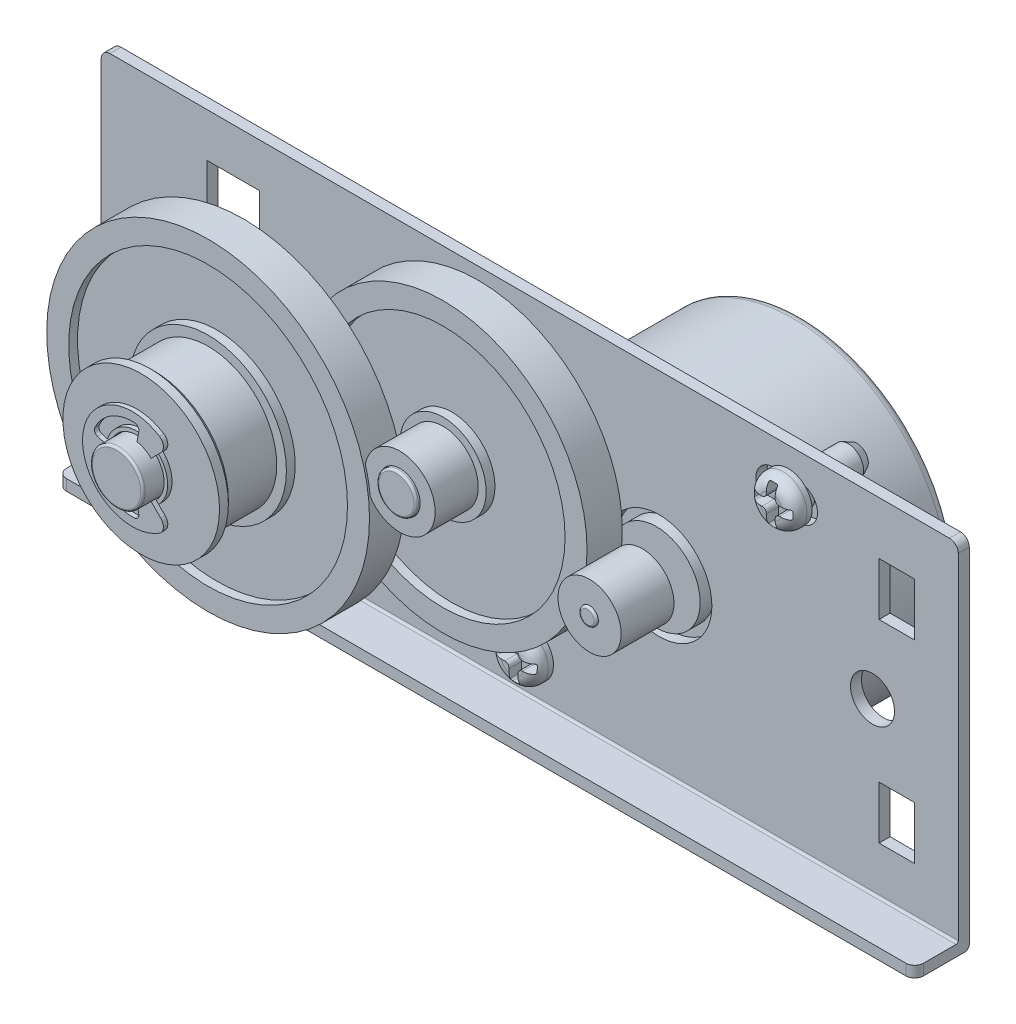
SolidWorks part; units mm, degrees
ref_plane "Plano frontal" through (0, 0, 0) normal (0, 0, 1) x (1, 0, 0)
ref_plane "Plano superior" through (0, 0, 0) normal (0, 1, 0) x (1, 0, 0)
ref_plane "Plano direito" through (0, 0, 0) normal (1, 0, 0) x (0, 0, -1)
sketch "Esboço1" plane through (0, 0, 0) normal (0, 0, 1) x (1, 0, 0)
  line L1 (48.7, 0.625) -> (-48.7, 0.625)
  line L2 (48.7, 0.625) -> (48.7, -0.625)
  line L3 (48.7, -0.625) -> (-48.7, -0.625)
  line L4 (-48.7, 0.625) -> (-48.7, -0.625)
  line L5 (48.7, 0.625) -> (-48.7, -0.625) construction
  line L6 (48.7, -0.625) -> (-48.7, 0.625) construction
  point P0 (0, 0)
  dimension "D1" = 97.4
  dimension "D2" = 1.25
extrude "Ressalto-extrusão1" add sketch "Esboço1" along normal blind 6.2
sketch "Esboço2" plane through (0, -0.625, 0) normal (0, 1, 0) x (1, 0, 0)
  line L0 (48.7, -6.2) -> (48.7, 0) construction
  line L1 (-48.7, 0) -> (48.7, 0)
  line L2 (-48.7, 0) -> (-48.7, -1.25)
  line L3 (-48.7, -1.25) -> (48.7, -1.25)
  line L4 (48.7, 0) -> (48.7, -1.25)
  dimension "D1" = 1.25
extrude "Ressalto-extrusão2" add sketch "Esboço2" along normal blind 40.6 contours L3 L4 L1 L2
fillet "Filete1" radius 1 4 edges at (48.7, 39.975, 0.625) (-48.7, 39.975, 0.625) (48.7, 0, 6.2) (-48.7, 0, 6.2)
sketch "Esboço3" plane through (0, 0, 1.25) normal (0, 0, 1) x (1, 0, 0)
  line L0 (27.7, 34.975) -> (30.7, 34.975) construction
  line L11 (39.7, 33.975) -> (43.7, 33.975)
  line L12 (39.7, 33.975) -> (39.7, 27.975)
  line L13 (39.7, 27.975) -> (43.7, 27.975)
  line L14 (43.7, 33.975) -> (43.7, 27.975)
  line L15 (39.7, 11.975) -> (43.7, 11.975)
  line L16 (39.7, 11.975) -> (39.7, 5.975)
  line L17 (39.7, 5.975) -> (43.7, 5.975)
  line L18 (43.7, 11.975) -> (43.7, 5.975)
  line L19 (-36.7, 12.975) -> (-30.7, 12.975)
  line L20 (-36.7, 12.975) -> (-36.7, 4.975)
  line L21 (-36.7, 4.975) -> (-30.7, 4.975)
  line L22 (-30.7, 12.975) -> (-30.7, 4.975)
  line L23 (27.7, 36.975) -> (30.7, 36.975)
  line L24 (27.7, 32.975) -> (30.7, 32.975)
  line L25 (0, 39.975) -> (0, 2.975) construction
  line L26 (-47.7, 39.975) -> (47.7, 39.975) construction
  line L27 (-47.7, 39.975) -> (47.7, 39.975) construction
  line L28 (-48.7, 38.975) -> (-48.7, 0.625) construction
  line L29 (-36.7, 34.975) -> (-30.7, 34.975)
  line L30 (-36.7, 34.975) -> (-36.7, 26.975)
  line L31 (-36.7, 26.975) -> (-30.7, 26.975)
  line L32 (-30.7, 34.975) -> (-30.7, 26.975)
  line L33 (48.7, 38.975) -> (48.7, 0.625) construction
  line L34 (48.7, 19.8) -> (0, 19.8) construction
  circle A5 centre (-43.7, 4.975) radius 2
  circle A6 centre (0, 4.975) radius 2
  circle A7 centre (38.95, 19.8) radius 2.5
  circle A8 centre (14.7, 19.8) radius 6
  arc A9 (27.7, 36.975) -> (27.7, 32.975) centre (27.7, 34.975) ccw
  arc A10 (30.7, 32.975) -> (30.7, 36.975) centre (30.7, 34.975) ccw
  point P22 (29.2, 34.975)
  point P33 (25.7, 34.975)
  point P34 (32.7, 34.975)
  dimension "D14" = 5
  dimension "D16" = 16
  dimension "D27" = 4
  dimension "D3" = 4
  dimension "D6" = 12
  dimension "D17" = 5
  dimension "D4" = 35
  dimension "D8" = 34
  dimension "D9" = 6
  dimension "D10" = 4
  dimension "D11" = 6
  dimension "D12" = 4
  dimension "D13" = 5
  dimension "D15" = 6
  dimension "D18" = 9.75
  dimension "D19" = 8
  dimension "D20" = 6
  dimension "D21" = 8
  dimension "D22" = 6
  dimension "D23" = 12
  dimension "D24" = 12
  dimension "D25" = 5
  dimension "D26" = 14
  dimension "D28" = 5
  dimension "D29" = 35
  dimension "D30" = 0
  dimension "D31" = 4
  dimension "D32" = 7
  dimension "D33" = 3
  dimension "D34" = 16
extrude "Corte-extrusão1" cut sketch "Esboço3" against normal blind 40.6
sketch "Esboço5" plane through (0, 0, 0) normal (0, 0, -1) x (-1, 0, 0)
  line L0 (-20.7, 19.8) -> (48.7, 19.8) construction
  line L1 (48.7, 38.975) -> (48.7, -0.625) construction
  line L2 (47.7, 39.975) -> (-47.7, 39.975) construction
  line L3 (48.7, 23.975) -> (48.7, 19.8) construction
  circle A0 centre (4.1, 23.975) radius 2
  circle A1 centre (25.7, 19.8) radius 3
  circle A2 centre (-14.7, 19.8) radius 6 construction
  dimension "D1" = 23
  dimension "6" = 6
  dimension "D2" = 4
  dimension "D3" = 16
  dimension "D4" = 44.6
sketch "Esboço6" plane through (0, 0, 0) normal (0, 0, -1) x (-1, 0, 0)
  circle A0 centre (25.7, 19.8) radius 3
  dimension "D1" = 6
extrude "Ressalto-extrusão3" add sketch "Esboço6" against normal blind 22.5
sketch "Esboço7" plane through (0, 0, 0) normal (0, 0, -1) x (-1, 0, 0)
  circle A0 centre (4.1, 23.975) radius 2.25
  dimension "D1" = 4.5
extrude "Ressalto-extrusão4" add sketch "Esboço7" against normal blind 12.3
fillet "Filete2" radius 0.25 2 edges at (-6.35, 23.975, 12.3) (-28.7, 19.8, 22.5)
sketch "Esboço12" plane through (0, 0, 0) normal (0, 0, 1) x (1, 0, 0)
  circle A0 centre (-4.1, 23.975) radius 4
  dimension "D1" = 8
extrude "Ressalto-extrusão7" add sketch "Esboço12" along normal blind 3
sketch "Esboço13" plane through (0, 0, 0) normal (0, 0, -1) x (-1, 0, 0)
  circle A0 centre (25.7, 19.8) radius 4.5
  dimension "D1" = 9
extrude "Ressalto-extrusão8" add sketch "Esboço13" against normal blind 8.1
sketch "Esboço8" plane through (0, 0, 3) normal (0, 0, 1) x (1, 0, 0)
  circle A0 centre (-4.1, 23.975) radius 16.365
  circle A1 centre (-4.1, 23.975) radius 2.3
  dimension "D1" = 32.73
  dimension "D2" = 4.6
extrude "Ressalto-extrusão5" add sketch "Esboço8" along normal blind 4
sketch "Esboço9" plane through (0, 0, 3) normal (0, 0, 1) x (1, 0, 0)
  circle A1 centre (-4.1, 23.975) radius 4
  circle A2 centre (-4.1, 23.975) radius 2.3
  dimension "D1" = 8
extrude "Ressalto-extrusão6" add sketch "Esboço9" along normal blind 8.9
sketch "Esboço10" plane through (0, 0, 7) normal (0, 0, 1) x (1, 0, 0)
  circle A0 centre (-4.1, 23.975) radius 4.9
  circle A1 centre (-4.1, 23.975) radius 13.865
  circle A2 centre (-4.1, 23.975) radius 16.365 construction
  dimension "D1" = 9.8
  dimension "D2" = 2.5
extrude "Corte-extrusão2" cut sketch "Esboço10" against normal blind 1
sketch "Esboço11" plane through (0, 0, 3) normal (0, 0, -1) x (-1, 0, 0)
  circle A1 centre (4.1, 23.975) radius 13.86
  circle A2 centre (4.1, 23.975) radius 4.9
extrude "Corte-extrusão3" cut sketch "Esboço11" against normal blind 1
sketch "Esboço14" plane through (0, 0, 8.1) normal (0, 0, 1) x (1, 0, 0)
  circle A0 centre (-25.7, 19.8) radius 18.34
  circle A1 centre (-25.7, 19.8) radius 3.1
  circle A2 centre (-25.7, 19.8) radius 3 construction
  dimension "D1" = 36.68
  dimension "D2" = 0.1
extrude "Ressalto-extrusão9" add sketch "Esboço14" along normal blind 4
sketch "Esboço15" plane through (0, 0, 8.1) normal (0, 0, 1) x (1, 0, 0)
  circle A0 centre (-25.7, 19.8) radius 7.8
  circle A1 centre (-25.7, 19.8) radius 3.1
  dimension "D1" = 15.6
extrude "Ressalto-extrusão10" add sketch "Esboço15" along normal blind 11.6
sketch "Esboço16" plane through (0, 0, 19.7) normal (0, 0, 1) x (1, 0, 0)
  circle A0 centre (-25.7, 19.8) radius 3.1
  circle A1 centre (-25.7, 19.8) radius 8.9
  dimension "D1" = 17.8
extrude "Ressalto-extrusão11" add sketch "Esboço16" against normal blind 1.5
chamfer "Chanfro1" distance 0.5 angle 45 1 edges at (-16.8, 19.8, 18.2)
sketch "Esboço17" plane through (0, 0, 19.7) normal (0, 0, 1) x (1, 0, 0)
  circle A0 centre (-25.7, 19.8) radius 3.1
  circle A1 centre (-25.7, 19.8) radius 3.5
  dimension "D1" = 7
extrude "Ressalto-extrusão12" add sketch "Esboço17" along normal blind 0.5
sketch "Esboço18" plane through (0, 0, 12.1) normal (0, 0, 1) x (1, 0, 0)
  circle A0 centre (-25.7, 19.8) radius 15.84
  circle A1 centre (-25.7, 19.8) radius 8.9
  circle A2 centre (-25.7, 19.8) radius 18.34 construction
  dimension "D1" = 2.5
  dimension "D2" = 17.8
extrude "Corte-extrusão4" cut sketch "Esboço18" against normal blind 1
sketch "Esboço19" plane through (0, 0, 8.1) normal (0, 0, -1) x (-1, 0, 0)
  circle A0 centre (25.7, 19.8) radius 8.9
  circle A1 centre (25.7, 19.8) radius 15.825
extrude "Corte-extrusão5" cut sketch "Esboço19" against normal blind 1
sketch "Esboço20" plane through (0, 0, 20.2) normal (0, 0, 1) x (1, 0, 0)
  line L0 (-28.3227, 20.6269) -> (-29.675, 21.0533)
  line L3 (-23.7555, 21.7445) -> (-22.4747, 23.0253)
  line L4 (-25.2225, 22.5082) -> (-24.9763, 23.9046)
  line L5 (-23.7555, 17.8555) -> (-22.4747, 16.5747)
  line L6 (-25.2225, 17.0918) -> (-24.9763, 15.6954)
  line L7 (-28.3227, 18.9731) -> (-29.675, 18.5467)
  arc A0 (-22.6425, 24.5746) -> (-22.6425, 15.0254) centre (-25.7, 19.8) ccw
  arc A1 (-25.4411, 24.4906) -> (-29.9802, 21.7362) centre (-25.7, 19.8) ccw
  arc A2 (-28.3227, 20.6269) -> (-28.3227, 18.9731) centre (-25.7, 19.8) ccw
  arc A3 (-23.7555, 21.7445) -> (-25.2225, 22.5082) centre (-25.7, 19.8) ccw
  arc A4 (-25.2225, 17.0918) -> (-23.7555, 17.8555) centre (-25.7, 19.8) ccw
  arc A5 (-29.9802, 17.8638) -> (-25.4411, 15.1094) centre (-25.7, 19.8) ccw
  arc A6 (-22.4747, 16.5747) -> (-22.6425, 15.0254) centre (-23.1818, 15.8675) cw
  arc A7 (-22.4747, 23.0253) -> (-22.6425, 24.5746) centre (-23.1818, 23.7325) ccw
  arc A8 (-25.4411, 15.1094) -> (-24.9763, 15.6954) centre (-25.4687, 15.6086) ccw
  arc A9 (-25.4411, 24.4906) -> (-24.9763, 23.9046) centre (-25.4687, 23.9914) cw
  arc A10 (-29.9802, 17.8638) -> (-29.675, 18.5467) centre (-29.5246, 18.0698) cw
  arc A11 (-29.9802, 21.7362) -> (-29.675, 21.0533) centre (-29.5246, 21.5302) ccw
  dimension "D2" = 1
  dimension "D3" = 0.5
  dimension "D1" = 35
  dimension "D4" = 35
  dimension "D5" = 35
extrude "Ressalto-extrusão13" add sketch "Esboço20" along normal blind 0.5
sketch "Esboço21" plane through (0, 0, 0) normal (0, 0, -1) x (-1, 0, 0)
  line L0 (-29.3939, 34.975) -> (0, 4.975) construction
  line L1 (3.3061, 4.975) -> (-3.6939, 4.975) construction
  line L2 (3.5952, 5.1615) -> (2.7796, 20.8817)
  line L3 (-13.4337, 37.4293) -> (-29.134, 38.5656)
  line L4 (0, 1.375) -> (-4.8727, 1.375)
  line L5 (-32.9939, 34.975) -> (-32.9939, 30.076)
  line L6 (-32.9939, 30.076) -> (-30.4878, 27.5182)
  line L7 (-7.4776, 4.0335) -> (-4.8727, 1.375)
  circle A2 centre (0, 4.975) radius 1.75
  circle A3 centre (-29.3939, 34.975) radius 1.75
  arc A4 (-30.4878, 27.5182) -> (-7.4776, 4.0335) centre (-14.6969, 19.975) ccw
  arc A5 (0, 1.375) -> (3.5952, 5.1615) centre (0, 4.975) ccw
  arc A7 (-29.134, 38.5656) -> (-32.9939, 34.975) centre (-29.3939, 34.975) ccw
  arc A9 (2.7796, 20.8817) -> (-13.4337, 37.4293) centre (-14.6969, 19.975) ccw
  dimension "D2" = 3.5
  dimension "D3" = 3.5
  dimension "D4" = 35
  dimension "D5" = 7.2
  dimension "D1" = 42
  dimension "D7" = 6
extrude "Ressalto-extrusão14" add sketch "Esboço21" along normal blind 0.92
sketch "Esboço23" plane through (0, 0, 0) normal (0, 0, 1) x (1, 0, 0)
  circle A0 centre (14.7, 19.8) radius 17.675
extrude "Ressalto-extrusão15" add sketch "Esboço23" against normal blind 15
fillet "Filete4" radius 1 1 edges at (32.375, 19.8, -15)
sketch "Esboço24" plane through (0, 0, -0.92) normal (0, 0, -1) x (-1, 0, 0)
  circle A0 centre (0, 4.975) radius 1.75
  circle A1 centre (0, 4.975) radius 2.05
  circle A2 centre (-29.3939, 34.975) radius 1.75
  circle A3 centre (-29.3939, 34.975) radius 2.05
  dimension "D1" = 0.3
  dimension "D2" = 0.3
extrude "Ressalto-extrusão16" add sketch "Esboço24" along normal blind 1
sketch "Esboço25" plane through (0, 0, -15) normal (0, 0, -1) x (-1, 0, 0)
  circle A0 centre (-14.7, 19.8) radius 2.5
  dimension "D1" = 5
extrude "Ressalto-extrusão17" add sketch "Esboço25" along normal blind 0.1
sketch "Esboço26" plane through (0, 0, -15.1) normal (0, 0, -1) x (-1, 0, 0)
  circle A0 centre (-14.7, 19.8) radius 1
  dimension "D1" = 2
extrude "Ressalto-extrusão18" add sketch "Esboço26" along normal blind 0.5
fillet "Filete6" radius 0.1 1 edges at (12.2, 19.8, -15.1)
sketch "Esboço27" plane through (0, 0, -15) normal (0, 0, 1) x (1, 0, 0)
  circle A0 centre (14.7, 19.8) radius 4.99
  dimension "D1" = 9.98
extrude "Ressalto-extrusão19" add sketch "Esboço27" along normal blind 16.57
sketch "Esboço28" plane through (0, 0, -15.6) normal (0, 0, -1) x (-1, 0, 0)
  circle A0 centre (-14.7, 19.8) radius 1
extrude "Ressalto-extrusão20" add sketch "Esboço28" against normal blind 25
fillet "Filete5" radius 0.25 2 edges at (13.7, 19.8, -15.6) (13.7, 19.8, 9.4)
ref_plane "Plano2" through (0, 0, 9.15) normal (0, 0, 1) x (1, 0, 0)
sketch "Esboço29" plane through (0, 0, 9.15) normal (0, 0, 1) x (1, 0, 0)
  circle A0 centre (14.7, 19.8) radius 3.59
  dimension "D1" = 7.18
extrude "Ressalto-extrusão21" add sketch "Esboço29" against normal blind 6
sketch "Esboço30" plane through (0, 0, 1.25) normal (0, 0, 1) x (1, 0, 0)
  circle A0 centre (0, 4.975) radius 2.7
  circle A1 centre (29.3939, 34.975) radius 2.7
  dimension "D1" = 5.4
  dimension "D2" = 5.4
extrude "Ressalto-extrusão22" add sketch "Esboço30" along normal blind 2
fillet "Filete7" radius 1.4 2 edges at (2.7, 4.975, 3.25) (32.0939, 34.975, 3.25)
sketch "Esboço31" plane through (0, 0, 3.25) normal (0, 0, 1) x (1, 0, 0)
  line L1 (29.0939, 37.175) -> (29.6939, 37.175)
  line L2 (28.8939, 36.975) -> (28.8939, 35.975)
  line L3 (29.0939, 32.775) -> (29.6939, 32.775)
  line L4 (29.8939, 36.975) -> (29.8939, 35.975)
  line L7 (31.3939, 35.475) -> (30.3939, 35.475)
  line L8 (31.5939, 35.275) -> (31.5939, 34.675)
  line L9 (31.3939, 34.475) -> (30.3939, 34.475)
  line L10 (27.1939, 35.275) -> (27.1939, 34.675)
  line L15 (28.8939, 33.975) -> (28.8939, 32.975)
  line L17 (29.8939, 33.975) -> (29.8939, 32.975)
  line L18 (28.3939, 35.475) -> (27.3939, 35.475)
  line L19 (28.3939, 34.475) -> (27.3939, 34.475)
  line L42 (-0.1421, 7.325) -> (0.4579, 7.325)
  line L43 (-0.3421, 7.125) -> (-0.3421, 6.125)
  line L44 (-0.1421, 2.925) -> (0.4579, 2.925)
  line L45 (0.6579, 7.125) -> (0.6579, 6.125)
  line L46 (2.1579, 5.625) -> (1.1579, 5.625)
  line L47 (2.3579, 5.425) -> (2.3579, 4.825)
  line L48 (2.1579, 4.625) -> (1.1579, 4.625)
  line L49 (-2.0421, 5.425) -> (-2.0421, 4.825)
  line L50 (-0.3421, 4.125) -> (-0.3421, 3.125)
  line L51 (0.6579, 4.125) -> (0.6579, 3.125)
  line L52 (-0.8421, 5.625) -> (-1.8421, 5.625)
  line L53 (-0.8421, 4.625) -> (-1.8421, 4.625)
  arc A0 (29.8939, 33.975) -> (30.3939, 34.475) centre (30.3939, 33.975) cw
  arc A1 (28.8939, 33.975) -> (28.3939, 34.475) centre (28.3939, 33.975) ccw
  arc A2 (29.8939, 35.975) -> (30.3939, 35.475) centre (30.3939, 35.975) ccw
  arc A3 (28.8939, 35.975) -> (28.3939, 35.475) centre (28.3939, 35.975) cw
  arc A4 (28.8939, 32.975) -> (29.0939, 32.775) centre (29.0939, 32.975) ccw
  arc A5 (29.6939, 32.775) -> (29.8939, 32.975) centre (29.6939, 32.975) ccw
  arc A6 (31.5939, 34.675) -> (31.3939, 34.475) centre (31.3939, 34.675) cw
  arc A7 (31.3939, 35.475) -> (31.5939, 35.275) centre (31.3939, 35.275) cw
  arc A8 (29.6939, 37.175) -> (29.8939, 36.975) centre (29.6939, 36.975) cw
  arc A9 (29.0939, 37.175) -> (28.8939, 36.975) centre (29.0939, 36.975) ccw
  arc A10 (27.3939, 35.475) -> (27.1939, 35.275) centre (27.3939, 35.275) ccw
  arc A11 (27.3939, 34.475) -> (27.1939, 34.675) centre (27.3939, 34.675) cw
  circle A24 centre (29.3939, 34.975) radius 1.3 construction
  arc A37 (0.6579, 4.125) -> (1.1579, 4.625) centre (1.1579, 4.125) cw
  arc A38 (-0.3421, 4.125) -> (-0.8421, 4.625) centre (-0.8421, 4.125) ccw
  arc A39 (0.6579, 6.125) -> (1.1579, 5.625) centre (1.1579, 6.125) ccw
  arc A40 (-0.3421, 6.125) -> (-0.8421, 5.625) centre (-0.8421, 6.125) cw
  arc A41 (-0.3421, 3.125) -> (-0.1421, 2.925) centre (-0.1421, 3.125) ccw
  arc A42 (0.4579, 2.925) -> (0.6579, 3.125) centre (0.4579, 3.125) ccw
  arc A43 (2.3579, 4.825) -> (2.1579, 4.625) centre (2.1579, 4.825) cw
  arc A44 (2.1579, 5.625) -> (2.3579, 5.425) centre (2.1579, 5.425) cw
  arc A45 (0.4579, 7.325) -> (0.6579, 7.125) centre (0.4579, 7.125) cw
  arc A46 (-0.1421, 7.325) -> (-0.3421, 7.125) centre (-0.1421, 7.125) ccw
  arc A47 (-1.8421, 5.625) -> (-2.0421, 5.425) centre (-1.8421, 5.425) ccw
  arc A48 (-1.8421, 4.625) -> (-2.0421, 4.825) centre (-1.8421, 4.825) cw
  point P0 (0, 4.975)
  point P6 (29.3939, 34.975)
  point P19 (28.8939, 34.475)
  point P24 (28.8939, 35.475)
  point P27 (28.8939, 32.775)
  point P30 (29.8939, 32.775)
  point P33 (31.5939, 34.475)
  point P36 (31.5939, 35.475)
  point P39 (29.8939, 37.175)
  point P44 (27.1939, 35.475)
  point P128 (0.1579, 5.125)
  point P133 (0.1579, 5.125)
  dimension "D5" = 0.5
  dimension "D6" = 0.2
  dimension "D9" = 0.5
  dimension "D10" = 0.2
  dimension "D1" = 4.4
  dimension "D2" = 4.4
  dimension "D3" = 1
  dimension "D4" = 1
extrude "Corte-extrusão6" cut sketch "Esboço31" against normal blind 1.4
sketch "Esboço32" plane through (0, 0, 1.25) normal (0, 0, -1) x (-1, 0, 0)
  circle A0 centre (0, 4.975) radius 1.75
  circle A1 centre (-29.3939, 34.975) radius 1.75
extrude "Ressalto-extrusão23" add sketch "Esboço32" along normal blind 7.8
chamfer "Chanfro2" distance 1 angle 25 2 edges at (-1.75, 4.975, -6.55) (27.6439, 34.975, -6.55) first distance on face at (-1.75, 4.975, -1.92) first distance on face at (27.6439, 34.975, -1.92)
sketch "Esboço33" plane through (0, 0, -0.92) normal (0, 0, -1) x (-1, 0, 0)
  line L1 (3.2243, 12.8461) -> (4.2922, 22.7889)
  line L2 (4.2922, 22.7889) -> (2.6901, 22.961)
  line L3 (3.2243, 12.8461) -> (1.6222, 13.0182)
  arc A4 (1.6222, 13.0182) -> (2.6901, 22.961) centre (-14.7, 19.8) ccw
  arc A7 (1.6222, 13.0182) -> (2.6901, 22.961) centre (-14.7, 19.8) ccw
  arc M4 (2.9127, 18.3164) -> (-7.2301, 3.781) centre (-14.7, 19.8) cw
  line M8 (3.5952, 5.1615) -> (2.9127, 18.3164)
  dimension "D1" = 10
  dimension "D2" = 90
extrude "Ressalto-extrusão24" add sketch "Esboço33" along normal blind 10 contours A4 L3 L1 L2 M8 | L3 M8 M4 region at (-3.4256, 19.3944, -0.92) region at (-2.6269, 14.5261, -0.92)
sketch "Esboço34" plane through (-1.8235, -0.1959, 0) normal (-0.9943, -0.1068, 0) x (0, 0, 1)
  line L0 (-5.92, 23.117) -> (-5.92, 13.117) construction
  line L1 (-10.92, 23.117) -> (-0.92, 23.117) construction
  line L2 (-10.92, 13.117) -> (-0.92, 13.117) construction
  circle A0 centre (-5.92, 18.117) radius 2
  dimension "D1" = 4
extrude "Ressalto-extrusão25" add sketch "Esboço34" along normal blind 5
sketch "Esboço35" plane through (0, 0, 12.1) normal (0, 0, 1) x (1, 0, 0)
  line L0 (-48.7, 38.975) -> (-48.7, 0.625) construction
  circle A0 centre (-398.7, 19.8) radius 7.8
  point P2 (-25.7, 19.8)
  dimension "D1" = 15.6
  dimension "D2" = 350
  dimension "D3" = 0
extrude "Ressalto-extrusão26" add sketch "Esboço35" along normal blind 7.6 separate body
sketch "Esboço37" plane through (0, 0, 19.7) normal (0, 0, 1) x (1, 0, 0)
  circle A0 centre (-398.7, 19.8) radius 8.9
  dimension "D1" = 17.8
extrude "Ressalto-extrusão27" add sketch "Esboço37" against normal blind 1.5
chamfer "Chanfro3" distance 0.5 angle 45 1 edges at (-389.8, 19.8, 18.2)
sketch "Esboço38" plane through (0, 0, 12.1) normal (0, 0, -1) x (-1, 0, 0)
  circle A0 centre (398.7, 19.8) radius 8.9
extrude "Ressalto-extrusão28" add sketch "Esboço38" along normal blind 1.5
sketch "Esboço39" plane through (0, 0, 19.7) normal (0, 0, 1) x (1, 0, 0)
  circle A0 centre (-398.7, 19.8) radius 3.05
  dimension "D1" = 6.1
extrude "Corte-extrusão7" cut sketch "Esboço39" against normal blind 35.5 and the other way blind 16
sketch "Esboço40" plane through (0, 0, 10.6) normal (0, 0, -1) x (-1, 0, 0)
  circle A0 centre (398.7, 19.8) radius 4
  dimension "D1" = 8
extrude "Ressalto-extrusão29" add sketch "Esboço40" along normal blind 6
sketch "Esboço41" plane through (0, 0, 4.6) normal (0, 0, -1) x (-1, 0, 0)
  circle A0 centre (398.7, 19.8) radius 3
  dimension "D1" = 6
extrude "Ressalto-extrusão30" add sketch "Esboço41" against normal blind 18.5
fillet "Filete8" radius 0.25 1 edges at (-401.7, 19.8, 23.1)
sketch "Esboço42" plane through (0, 0, 19.7) normal (0, 0, 1) x (1, 0, 0)
  line L6 (-401.3227, 20.6269) -> (-402.675, 21.0533)
  line L7 (-396.7555, 21.7445) -> (-395.4747, 23.0253)
  line L8 (-398.2225, 22.5082) -> (-397.9763, 23.9046)
  line L9 (-396.7555, 17.8555) -> (-395.4747, 16.5747)
  line L10 (-398.2225, 17.0918) -> (-397.9763, 15.6954)
  line L11 (-401.3227, 18.9731) -> (-402.675, 18.5467)
  arc A12 (-395.6425, 24.5746) -> (-395.6425, 15.0254) centre (-398.7, 19.8) ccw
  arc A13 (-398.4411, 24.4906) -> (-402.9802, 21.7362) centre (-398.7, 19.8) ccw
  arc A14 (-401.3227, 20.6269) -> (-401.3227, 18.9731) centre (-398.7, 19.8) ccw
  arc A15 (-396.7555, 21.7445) -> (-398.2225, 22.5082) centre (-398.7, 19.8) ccw
  arc A16 (-398.2225, 17.0918) -> (-396.7555, 17.8555) centre (-398.7, 19.8) ccw
  arc A17 (-402.9802, 17.8638) -> (-398.4411, 15.1094) centre (-398.7, 19.8) ccw
  arc A18 (-395.4747, 16.5747) -> (-395.6425, 15.0254) centre (-396.1818, 15.8675) cw
  arc A19 (-395.4747, 23.0253) -> (-395.6425, 24.5746) centre (-396.1818, 23.7325) ccw
  arc A20 (-398.4411, 15.1094) -> (-397.9763, 15.6954) centre (-398.4687, 15.6086) ccw
  arc A21 (-398.4411, 24.4906) -> (-397.9763, 23.9046) centre (-398.4687, 23.9914) cw
  arc A22 (-402.9802, 17.8638) -> (-402.675, 18.5467) centre (-402.5246, 18.0698) cw
  arc A23 (-402.9802, 21.7362) -> (-402.675, 21.0533) centre (-402.5246, 21.5302) ccw
  point P0 (-398.7, 19.8)
  dimension "D4" = 1
  dimension "D5" = 0.5
  dimension "D1" = 35
  dimension "D2" = 35
  dimension "D3" = 35
extrude "Ressalto-extrusão31" add sketch "Esboço42" along normal blind 0.5
sketch "Esboço43" plane through (0, 0, 4.6) normal (0, 0, -1) x (-1, 0, 0)
  line L0 (402.2, 5.8) -> (402.2, 3.8)
  line L1 (408.7, 29.8) -> (388.7, 29.8)
  line L2 (408.7, 29.8) -> (408.7, 5.8)
  line L3 (408.7, 5.8) -> (402.2, 5.8)
  line L4 (388.7, 29.8) -> (388.7, 5.8)
  line L5 (395.2, 5.8) -> (388.7, 5.8)
  line L6 (408.7, 19.8) -> (388.7, 19.8) construction
  line L9 (395.2, 3.8) -> (402.2, 3.8)
  line L11 (398.7, 29.8) -> (398.7, 19.8) construction
  line L14 (395.2, 5.8) -> (395.2, 3.8)
  point P0 (398.7, 19.8)
  dimension "D1" = 20
  dimension "D2" = 24
  dimension "D4" = 7
  dimension "D5" = 26
extrude "Ressalto-extrusão32" add sketch "Esboço43" along normal blind 1.2 contours L1 L4 L5 L14 L9 L0 L3 L2
fillet "Filete9" radius 2 4 edges at (-408.7, 5.8, 4) (-388.7, 5.8, 4) (-388.7, 29.8, 4) (-408.7, 29.8, 4)
fillet "Filete10" radius 0.3 2 edges at (-402.2, 5.8, 4) (-395.2, 5.8, 4)
ref_plane "Plano3" through (0, 0, 13.1) normal (0, 0, 1) x (1, 0, 0)
sketch "Esboço45" plane through (0, 0, 3.4) normal (0, 0, -1) x (-1, 0, 0)
  line L0 (398.7, 3.8) -> (398.7, 29.8) construction
  line L1 (395.2, 3.8) -> (402.2, 3.8) construction
  line L2 (406.7, 29.8) -> (390.7, 29.8) construction
  line L4 (388.7, 27.8) -> (388.7, 7.8) construction
  line L5 (388.7, 17.8) -> (408.7, 17.8) construction
  line L6 (408.7, 27.8) -> (408.7, 7.8) construction
fillet "Filete11" radius 0.5 1 edges at (0, -0.625, 0)
fillet "Filete12" radius 0.25 1 edges at (0, 0.625, 1.25)
delete or keep bodies "Corpo-Excluir/Manter 1" type delete bodies bodies 139
